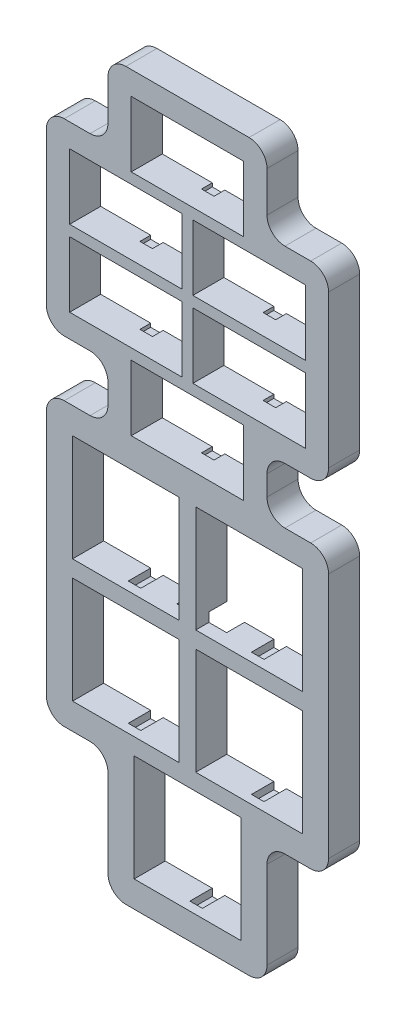
SolidWorks part; units mm, degrees
ref_plane "Front Plane" through (0, 0, 0) normal (0, 0, 1) x (1, 0, 0)
ref_plane "Top Plane" through (0, 0, 0) normal (0, 1, 0) x (1, 0, 0)
ref_plane "Right Plane" through (0, 0, 0) normal (1, 0, 0) x (0, 0, -1)
sketch "Sketch1" plane through (0, 0, 0) normal (0, 0, 1) x (1, 0, 0)
  line L0 (15.1765, -101.5047) -> (15.1765, -87.4077) construction
  line L1 (29.2735, -101.5047) -> (15.1765, -101.5047) construction
  line L2 (29.2735, -101.5047) -> (29.2735, -87.4077) construction
  line L3 (29.2735, -87.4077) -> (15.1765, -87.4077) construction
  line L4 (15.1765, -101.5047) -> (15.1765, -87.4077) construction
  line L5 (29.7815, -102.0127) -> (14.6685, -102.0127)
  line L6 (14.6685, -102.0127) -> (14.6685, -86.8997)
  line L7 (29.7815, -86.8997) -> (14.6685, -86.8997)
  line L8 (20.5423, -84.0423) -> (6.4453, -84.0423) construction
  line L9 (20.5423, -84.0423) -> (20.5423, -69.9453) construction
  line L10 (20.5423, -69.9453) -> (6.4453, -69.9453) construction
  line L11 (6.4453, -84.0423) -> (6.4453, -69.9453) construction
  line L12 (29.7815, -102.0127) -> (29.7815, -86.8997)
  line L13 (21.0503, -84.5503) -> (5.9373, -84.5503)
  line L14 (23.9078, -84.0422) -> (38.0048, -84.0422) construction
  line L15 (23.9078, -84.0422) -> (23.9078, -69.9452) construction
  line L16 (23.9078, -69.9452) -> (38.0048, -69.9452) construction
  line L17 (38.0048, -84.0422) -> (38.0048, -69.9452) construction
  line L18 (5.9373, -84.5503) -> (5.9373, -69.4373)
  line L19 (21.0503, -69.4373) -> (5.9373, -69.4373)
  line L20 (38.0048, -66.5797) -> (23.9078, -66.5797) construction
  line L21 (38.0048, -66.5797) -> (38.0048, -52.4827) construction
  line L22 (38.0048, -52.4827) -> (23.9078, -52.4827) construction
  line L23 (23.9078, -66.5797) -> (23.9078, -52.4827) construction
  line L24 (21.0503, -84.5503) -> (21.0503, -69.4373)
  line L25 (23.3998, -84.5502) -> (38.5128, -84.5502)
  line L26 (20.5423, -66.5798) -> (6.4453, -66.5797) construction
  line L27 (20.5423, -66.5798) -> (20.5423, -52.4827) construction
  line L28 (20.5423, -52.4827) -> (6.4453, -52.4828) construction
  line L29 (6.4453, -66.5797) -> (6.4453, -52.4828) construction
  line L30 (38.5128, -84.5502) -> (38.5128, -69.4372)
  line L31 (23.3998, -69.4372) -> (38.5128, -69.4372)
  line L32 (29.6863, -47.3075) -> (14.7638, -47.3075) construction
  line L33 (29.6863, -47.3075) -> (29.6863, -39.0525) construction
  line L34 (29.6863, -39.0525) -> (14.7638, -39.0525) construction
  line L35 (14.7638, -47.3075) -> (14.7638, -39.0525) construction
  line L36 (23.3998, -84.5502) -> (23.3998, -69.4372)
  line L37 (38.5128, -67.0877) -> (23.3998, -67.0877)
  line L38 (20.955, -36.5125) -> (6.0325, -36.5125) construction
  line L39 (20.955, -36.5125) -> (20.955, -28.2575) construction
  line L40 (20.955, -28.2575) -> (6.0325, -28.2575) construction
  line L41 (6.0325, -36.5125) -> (6.0325, -28.2575) construction
  line L42 (23.3998, -67.0877) -> (23.3998, -51.9747)
  line L43 (38.5128, -51.9747) -> (23.3998, -51.9747)
  line L44 (20.955, -25.7175) -> (6.0325, -25.7175) construction
  line L45 (20.955, -25.7175) -> (20.955, -17.4625) construction
  line L46 (20.955, -17.4625) -> (6.0325, -17.4625) construction
  line L47 (6.0325, -25.7175) -> (6.0325, -17.4625) construction
  line L48 (38.5128, -67.0877) -> (38.5128, -51.9747)
  line L49 (21.0503, -67.0877) -> (5.9373, -67.0877)
  line L50 (29.6863, -14.9225) -> (14.7638, -14.9225) construction
  line L51 (29.6863, -14.9225) -> (29.6863, -6.6675) construction
  line L52 (29.6863, -6.6675) -> (14.7638, -6.6675) construction
  line L53 (14.7638, -14.9225) -> (14.7638, -6.6675) construction
  line L54 (5.9373, -67.0877) -> (5.9373, -51.9747)
  line L55 (21.0503, -51.9747) -> (5.9373, -51.9747)
  line L56 (38.4175, -25.7175) -> (23.495, -25.7175) construction
  line L57 (38.4175, -25.7175) -> (38.4175, -17.4625) construction
  line L58 (38.4175, -17.4625) -> (23.495, -17.4625) construction
  line L59 (23.495, -25.7175) -> (23.495, -17.4625) construction
  line L60 (21.0503, -67.0877) -> (21.0503, -51.9747)
  line L61 (30.1943, -47.8155) -> (14.2558, -47.8155)
  line L62 (38.4175, -36.5125) -> (23.495, -36.5125) construction
  line L63 (38.4175, -36.5125) -> (38.4175, -28.2575) construction
  line L64 (38.4175, -28.2575) -> (23.495, -28.2575) construction
  line L65 (23.495, -36.5125) -> (23.495, -28.2575) construction
  line L66 (14.2558, -47.8155) -> (14.2558, -38.5445)
  line L67 (30.1943, -38.5445) -> (14.2558, -38.5445)
  line L68 (30.1943, -47.8155) -> (30.1943, -38.5445)
  line L69 (21.463, -37.0205) -> (5.5245, -37.0205)
  line L70 (5.5245, -37.0205) -> (5.5245, -27.7495)
  line L71 (21.463, -27.7495) -> (5.5245, -27.7495)
  line L72 (21.463, -37.0205) -> (21.463, -27.7495)
  line L73 (21.463, -26.2255) -> (5.5245, -26.2255)
  line L74 (5.5245, -26.2255) -> (5.5245, -16.9545)
  line L75 (21.463, -16.9545) -> (5.5245, -16.9545)
  line L76 (21.463, -26.2255) -> (21.463, -16.9545)
  line L77 (30.1943, -15.4305) -> (14.2558, -15.4305)
  line L78 (14.2558, -15.4305) -> (14.2558, -6.1595)
  line L79 (30.1943, -6.1595) -> (14.2558, -6.1595)
  line L80 (30.1943, -15.4305) -> (30.1943, -6.1595)
  line L81 (38.9255, -26.2255) -> (22.987, -26.2255)
  line L82 (22.987, -26.2255) -> (22.987, -16.9545)
  line L83 (38.9255, -16.9545) -> (22.987, -16.9545)
  line L84 (38.9255, -26.2255) -> (38.9255, -16.9545)
  line L85 (38.9255, -37.0205) -> (22.987, -37.0205)
  line L86 (22.987, -37.0205) -> (22.987, -27.7495)
  line L87 (38.9255, -27.7495) -> (22.987, -27.7495)
  line L88 (38.9255, -37.0205) -> (38.9255, -27.7495)
  line L97 (30.9563, -85.725) -> (39.6875, -85.725)
  line L98 (39.6875, -85.725) -> (39.6875, -50.8)
  line L99 (39.6875, -50.8) -> (4.7625, -50.8)
  line L100 (4.7625, -50.8) -> (4.7625, -85.725)
  line L101 (30.9563, -37.7825) -> (39.6875, -37.7825)
  line L102 (39.6875, -37.7825) -> (39.6875, -16.1925)
  line L103 (39.6875, -16.1925) -> (30.9563, -16.1925)
  line L104 (30.9563, -16.1925) -> (30.9563, -5.3975)
  line L105 (30.9563, -5.3975) -> (13.4938, -5.3975)
  line L106 (13.4938, -5.3975) -> (13.4938, -16.1925)
  line L107 (13.4938, -16.1925) -> (4.7625, -16.1925)
  line L108 (4.7625, -16.1925) -> (4.7625, -37.7825)
  line L109 (4.7625, -37.7825) -> (13.4938, -37.7825)
  line L110 (13.4938, -37.7825) -> (13.4938, -48.5775)
  line L111 (13.4938, -48.5775) -> (30.9563, -48.5775)
  line L112 (30.9563, -48.5775) -> (30.9563, -37.7825)
  line L113 (30.9563, -37.7825) -> (39.6875, -37.7825)
  line L114 (39.6875, -37.7825) -> (39.6875, -16.1925)
  line L115 (39.6875, -16.1925) -> (30.9563, -16.1925)
  line L116 (30.9563, -16.1925) -> (30.9563, -5.3975)
  line L117 (30.9563, -5.3975) -> (13.4938, -5.3975)
  line L118 (13.4938, -5.3975) -> (13.4938, -16.1925)
  line L119 (13.4938, -16.1925) -> (4.7625, -16.1925)
  line L120 (4.7625, -16.1925) -> (4.7625, -37.7825)
  line L121 (4.7625, -37.7825) -> (13.4938, -37.7825)
  line L122 (13.4938, -37.7825) -> (13.4938, -48.5775)
  line L124 (30.9563, -48.5775) -> (30.9563, -37.7825)
  line L125 (4.7625, -85.725) -> (13.4938, -85.725)
  line L126 (13.4938, -85.725) -> (13.4938, -103.1875)
  line L127 (13.4938, -103.1875) -> (30.9563, -103.1875)
  line L128 (30.9563, -103.1875) -> (30.9563, -85.725)
  line L129 (30.9563, -85.725) -> (39.6875, -85.725)
  line L130 (39.6875, -85.725) -> (39.6875, -50.8)
  line L131 (39.6875, -50.8) -> (30.9563, -50.8)
  line L132 (4.7625, -50.8) -> (4.7625, -85.725)
  line L133 (4.7625, -85.725) -> (13.4938, -85.725)
  line L134 (13.4938, -85.725) -> (13.4938, -103.1875)
  line L135 (13.4938, -103.1875) -> (30.9563, -103.1875)
  line L136 (30.9563, -103.1875) -> (30.9563, -85.725)
  line L2229 (13.4938, -50.8) -> (4.7625, -50.8)
  line L2231 (30.9563, -48.5775) -> (30.9563, -50.8)
  line L2233 (13.4938, -48.5775) -> (13.4938, -50.8)
  dimension "D1" = 0.508
  dimension "D2" = 0
  dimension "D3" = 0
extrude "Boss-Extrude1" add sketch "Sketch1" against normal up to surface (4.4025 mm away)
sketch "Sketch4" plane through (0, 0, -4.4025) normal (0, 0, -1) x (-1, 0, 0)
  line L40 (-30.9563, -37.7825) -> (-30.9563, -50.8)
  line L41 (-30.9563, -50.8) -> (-39.6875, -50.8)
  line L42 (-39.6875, -50.8) -> (-39.6875, -85.725)
  line L43 (-39.6875, -85.725) -> (-30.9563, -85.725)
  line L44 (-30.9563, -85.725) -> (-30.9563, -103.1875)
  line L45 (-30.9563, -103.1875) -> (-13.4938, -103.1875)
  line L46 (-13.4938, -103.1875) -> (-13.4938, -85.725)
  line L47 (-13.4938, -85.725) -> (-4.7625, -85.725)
  line L48 (-4.7625, -85.725) -> (-4.7625, -50.8)
  line L49 (-4.7625, -50.8) -> (-13.4938, -50.8)
  line L50 (-13.4938, -50.8) -> (-13.4938, -37.7825)
  line L51 (-13.4938, -37.7825) -> (-4.7625, -37.7825)
  line L52 (-4.7625, -37.7825) -> (-4.7625, -16.1925)
  line L53 (-4.7625, -16.1925) -> (-13.4938, -16.1925)
  line L54 (-13.4938, -16.1925) -> (-13.4938, -5.3975)
  line L55 (-13.4938, -5.3975) -> (-30.9563, -5.3975)
  line L56 (-30.9563, -5.3975) -> (-30.9563, -16.1925)
  line L57 (-30.9563, -16.1925) -> (-39.6875, -16.1925)
  line L58 (-39.6875, -16.1925) -> (-39.6875, -37.7825)
  line L59 (-39.6875, -37.7825) -> (-30.9563, -37.7825)
  line L60 (-30.9563, -37.7825) -> (-30.9563, -50.8)
  line L61 (-30.9563, -50.8) -> (-39.6875, -50.8)
  line L62 (-39.6875, -50.8) -> (-39.6875, -85.725)
  line L63 (-39.6875, -85.725) -> (-30.9563, -85.725)
  line L64 (-30.9563, -85.725) -> (-30.9563, -103.1875)
  line L65 (-30.9563, -103.1875) -> (-13.4938, -103.1875)
  line L66 (-13.4938, -103.1875) -> (-13.4938, -85.725)
  line L67 (-13.4938, -85.725) -> (-4.7625, -85.725)
  line L68 (-4.7625, -85.725) -> (-4.7625, -50.8)
  line L69 (-4.7625, -50.8) -> (-13.4938, -50.8)
  line L70 (-13.4938, -50.8) -> (-13.4938, -37.7825)
  line L71 (-13.4938, -37.7825) -> (-4.7625, -37.7825)
  line L72 (-4.7625, -37.7825) -> (-4.7625, -16.1925)
  line L73 (-4.7625, -16.1925) -> (-13.4938, -16.1925)
  line L74 (-13.4938, -16.1925) -> (-13.4938, -5.3975)
  line L75 (-13.4938, -5.3975) -> (-30.9563, -5.3975)
  line L76 (-30.9563, -5.3975) -> (-30.9563, -16.1925)
  line L77 (-30.9563, -16.1925) -> (-39.6875, -16.1925)
  line L78 (-39.6875, -16.1925) -> (-39.6875, -37.7825)
  line L79 (-39.6875, -37.7825) -> (-30.9563, -37.7825)
  dimension "D1" = 0
extrude "Extrude-Thin1" add sketch "Sketch4" against normal through all thin thin type one direction wall 2.54
fillet "Fillet1" radius 2.54 20 edges at (42.2275, -48.26, -2.2012) (2.2225, -13.6525, -2.2012) (10.9538, -2.8575, -2.2012) (33.4963, -2.8575, -2.2012) (42.2275, -13.6525, -2.2012) (42.2275, -40.3225, -2.2012) (2.2225, -40.3225, -2.2012) (2.2225, -48.26, -2.2012) (42.2275, -88.265, -2.2012) (33.4963, -105.7275, -2.2012) (10.9538, -105.7275, -2.2012) (2.2225, -88.265, -2.2012) (10.9538, -88.265, -2.2012) (33.4963, -88.265, -2.2012) (33.4963, -40.3225, -2.2012) (33.4963, -48.26, -2.2012) (10.9538, -48.26, -2.2012) (10.9538, -40.3225, -2.2012) (10.9538, -13.6525, -2.2012) (33.4963, -13.6525, -2.2012)
sketch "Sketch5" plane through (0, 0, -4.4025) normal (0, 0, -1) x (-1, 0, 0)
  line L0 (-14.2558, -6.1595) -> (-30.1943, -6.1595) construction
  line L1 (-26.5906, -6.1595) -> (-25.3206, -6.1595) construction
  line L2 (-26.5906, -6.1595) -> (-26.5906, -5.9065) construction
  line L3 (-26.5906, -5.9065) -> (-25.3206, -5.9065) construction
  line L4 (-25.3206, -6.1595) -> (-25.3206, -5.9065) construction
  line L5 (-19.1294, -6.1595) -> (-17.8594, -6.1595) construction
  line L6 (-19.1294, -6.1595) -> (-19.1294, -5.9065) construction
  line L7 (-19.1294, -5.9065) -> (-17.8594, -5.9065) construction
  line L8 (-17.8594, -6.1595) -> (-17.8594, -5.9065) construction
  line L9 (-21.59, -15.6835) -> (-21.59, -15.4305) construction
  line L10 (-22.86, -15.6835) -> (-21.59, -15.6835) construction
  line L11 (-22.86, -15.6835) -> (-22.86, -15.4305) construction
  line L12 (-22.86, -15.4305) -> (-21.59, -15.4305) construction
  line L13 (-35.3219, -16.7015) -> (-34.0519, -16.7015) construction
  line L14 (-27.8606, -16.7015) -> (-26.5906, -16.7015) construction
  line L15 (-30.3213, -26.4785) -> (-30.3213, -26.2255) construction
  line L16 (-31.5913, -26.4785) -> (-30.3213, -26.4785) construction
  line L17 (-35.3219, -16.9545) -> (-34.0519, -16.9545) construction
  line L18 (-34.0519, -16.9545) -> (-34.0519, -16.7015) construction
  line L19 (-27.8606, -16.9545) -> (-26.5906, -16.9545) construction
  line L20 (-26.5906, -16.9545) -> (-26.5906, -16.7015) construction
  line L21 (-31.5913, -26.2255) -> (-30.3213, -26.2255) construction
  line L22 (-27.8606, -16.9545) -> (-27.8606, -16.7015) construction
  line L23 (-31.5913, -26.4785) -> (-31.5913, -26.2255) construction
  line L24 (-35.3219, -16.9545) -> (-35.3219, -16.7015) construction
  line L25 (-12.8588, -26.4785) -> (-12.8588, -26.2255) construction
  line L26 (-16.5894, -16.9545) -> (-16.5894, -16.7015) construction
  line L27 (-10.3981, -16.9545) -> (-10.3981, -16.7015) construction
  line L28 (-14.1288, -26.4785) -> (-12.8588, -26.4785) construction
  line L29 (-14.1288, -26.4785) -> (-14.1288, -26.2255) construction
  line L30 (-17.8594, -16.7015) -> (-16.5894, -16.7015) construction
  line L31 (-9.1281, -16.9545) -> (-9.1281, -16.7015) construction
  line L32 (-14.1288, -26.2255) -> (-12.8588, -26.2255) construction
  line L33 (-17.8594, -16.9545) -> (-16.5894, -16.9545) construction
  line L34 (-10.3981, -16.9545) -> (-9.1281, -16.9545) construction
  line L35 (-17.8594, -16.9545) -> (-17.8594, -16.7015) construction
  line L36 (-10.3981, -16.7015) -> (-9.1281, -16.7015) construction
  line L37 (-30.3213, -37.2735) -> (-30.3213, -37.0205) construction
  line L38 (-31.5913, -37.2735) -> (-31.5913, -37.0205) construction
  line L39 (-27.8606, -27.7495) -> (-26.5906, -27.7495) construction
  line L40 (-10.3981, -27.7495) -> (-10.3981, -27.4965) construction
  line L41 (-17.8594, -27.4965) -> (-16.5894, -27.4965) construction
  line L42 (-31.5913, -37.0205) -> (-30.3213, -37.0205) construction
  line L43 (-14.1287, -37.2735) -> (-12.8587, -37.2735) construction
  line L44 (-35.3219, -27.4965) -> (-34.0519, -27.4965) construction
  line L45 (-31.5913, -37.2735) -> (-30.3213, -37.2735) construction
  line L46 (-12.8587, -37.2735) -> (-12.8587, -37.0205) construction
  line L47 (-26.5906, -27.7495) -> (-26.5906, -27.4965) construction
  line L48 (-9.1281, -27.7495) -> (-9.1281, -27.4965) construction
  line L49 (-16.5894, -27.7495) -> (-16.5894, -27.4965) construction
  line L50 (-17.8594, -27.7495) -> (-16.5894, -27.7495) construction
  line L51 (-27.8606, -27.7495) -> (-27.8606, -27.4965) construction
  line L52 (-10.3981, -27.7495) -> (-9.1281, -27.7495) construction
  line L53 (-34.0519, -27.7495) -> (-34.0519, -27.4965) construction
  line L54 (-35.3219, -27.7495) -> (-35.3219, -27.4965) construction
  line L55 (-17.8594, -27.7495) -> (-17.8594, -27.4965) construction
  line L56 (-35.3219, -27.7495) -> (-34.0519, -27.7495) construction
  line L57 (-14.1287, -37.2735) -> (-14.1287, -37.0205) construction
  line L58 (-14.1287, -37.0205) -> (-12.8587, -37.0205) construction
  line L59 (-27.8606, -27.4965) -> (-26.5906, -27.4965) construction
  line L60 (-10.3981, -27.4965) -> (-9.1281, -27.4965) construction
  line L61 (-22.86, -47.8155) -> (-21.59, -47.8155) construction
  line L62 (-26.5906, -38.5445) -> (-26.5906, -38.2915) construction
  line L63 (-21.59, -48.0685) -> (-21.59, -47.8155) construction
  line L64 (-25.3206, -38.5445) -> (-25.3206, -38.2915) construction
  line L65 (-22.86, -48.0685) -> (-21.59, -48.0685) construction
  line L66 (-19.1294, -38.5445) -> (-17.8594, -38.5445) construction
  line L67 (-19.1294, -38.2915) -> (-17.8594, -38.2915) construction
  line L68 (-26.5906, -38.5445) -> (-25.3206, -38.5445) construction
  line L69 (-22.86, -48.0685) -> (-22.86, -47.8155) construction
  line L70 (-19.1294, -38.5445) -> (-19.1294, -38.2915) construction
  line L71 (-17.8594, -38.5445) -> (-17.8594, -38.2915) construction
  line L72 (-26.5906, -38.2915) -> (-25.3206, -38.2915) construction
  line L73 (-26.8446, -6.4135) -> (-25.0666, -6.4135)
  line L74 (-25.0666, -6.4135) -> (-25.0666, -5.6525)
  line L75 (-26.8446, -5.6525) -> (-25.0666, -5.6525)
  line L76 (-26.8446, -6.4135) -> (-26.8446, -5.6525)
  line L77 (-19.3834, -6.4135) -> (-17.6054, -6.4135)
  line L78 (-17.6054, -6.4135) -> (-17.6054, -5.6525)
  line L79 (-19.3834, -5.6525) -> (-17.6054, -5.6525)
  line L80 (-19.3834, -6.4135) -> (-19.3834, -5.6525)
  line L81 (-21.336, -15.9375) -> (-21.336, -15.1765)
  line L82 (-23.114, -15.1765) -> (-21.336, -15.1765)
  line L83 (-23.114, -15.9375) -> (-23.114, -15.1765)
  line L84 (-23.114, -15.9375) -> (-21.336, -15.9375)
  line L85 (-35.5759, -16.4475) -> (-33.7979, -16.4475)
  line L86 (-33.7979, -17.2085) -> (-33.7979, -16.4475)
  line L87 (-35.5759, -17.2085) -> (-33.7979, -17.2085)
  line L88 (-35.5759, -17.2085) -> (-35.5759, -16.4475)
  line L89 (-28.1146, -16.4475) -> (-26.3366, -16.4475)
  line L90 (-26.3366, -17.2085) -> (-26.3366, -16.4475)
  line L91 (-28.1146, -17.2085) -> (-26.3366, -17.2085)
  line L92 (-28.1146, -17.2085) -> (-28.1146, -16.4475)
  line L93 (-30.0673, -26.7325) -> (-30.0673, -25.9715)
  line L94 (-31.8453, -25.9715) -> (-30.0673, -25.9715)
  line L95 (-31.8453, -26.7325) -> (-31.8453, -25.9715)
  line L96 (-31.8453, -26.7325) -> (-30.0673, -26.7325)
  line L97 (-12.6048, -26.7325) -> (-12.6048, -25.9715)
  line L98 (-14.3828, -25.9715) -> (-12.6048, -25.9715)
  line L99 (-14.3828, -26.7325) -> (-14.3828, -25.9715)
  line L100 (-14.3828, -26.7325) -> (-12.6048, -26.7325)
  line L101 (-16.3354, -17.2085) -> (-16.3354, -16.4475)
  line L102 (-18.1134, -16.4475) -> (-16.3354, -16.4475)
  line L103 (-18.1134, -17.2085) -> (-18.1134, -16.4475)
  line L104 (-18.1134, -17.2085) -> (-16.3354, -17.2085)
  line L105 (-10.6521, -17.2085) -> (-10.6521, -16.4475)
  line L106 (-10.6521, -16.4475) -> (-8.8741, -16.4475)
  line L107 (-8.8741, -17.2085) -> (-8.8741, -16.4475)
  line L108 (-10.6521, -17.2085) -> (-8.8741, -17.2085)
  line L109 (-30.0673, -37.5275) -> (-30.0673, -36.7665)
  line L110 (-31.8453, -36.7665) -> (-30.0673, -36.7665)
  line L111 (-31.8453, -37.5275) -> (-31.8453, -36.7665)
  line L112 (-31.8453, -37.5275) -> (-30.0673, -37.5275)
  line L113 (-28.1146, -28.0035) -> (-26.3366, -28.0035)
  line L114 (-26.3366, -28.0035) -> (-26.3366, -27.2425)
  line L115 (-28.1146, -27.2425) -> (-26.3366, -27.2425)
  line L116 (-28.1146, -28.0035) -> (-28.1146, -27.2425)
  line L117 (-10.6521, -28.0035) -> (-10.6521, -27.2425)
  line L118 (-10.6521, -27.2425) -> (-8.8741, -27.2425)
  line L119 (-8.8741, -28.0035) -> (-8.8741, -27.2425)
  line L120 (-10.6521, -28.0035) -> (-8.8741, -28.0035)
  line L121 (-18.1134, -27.2425) -> (-16.3354, -27.2425)
  line L122 (-16.3354, -28.0035) -> (-16.3354, -27.2425)
  line L123 (-18.1134, -28.0035) -> (-16.3354, -28.0035)
  line L124 (-18.1134, -28.0035) -> (-18.1134, -27.2425)
  line L125 (-14.3827, -37.5275) -> (-12.6047, -37.5275)
  line L126 (-12.6047, -37.5275) -> (-12.6047, -36.7665)
  line L127 (-14.3827, -36.7665) -> (-12.6047, -36.7665)
  line L128 (-14.3827, -37.5275) -> (-14.3827, -36.7665)
  line L129 (-35.5759, -27.2425) -> (-33.7979, -27.2425)
  line L130 (-33.7979, -28.0035) -> (-33.7979, -27.2425)
  line L131 (-35.5759, -28.0035) -> (-33.7979, -28.0035)
  line L132 (-35.5759, -28.0035) -> (-35.5759, -27.2425)
  line L133 (-23.114, -47.5615) -> (-21.336, -47.5615)
  line L134 (-21.336, -48.3225) -> (-21.336, -47.5615)
  line L135 (-23.114, -48.3225) -> (-21.336, -48.3225)
  line L136 (-23.114, -48.3225) -> (-23.114, -47.5615)
  line L137 (-26.8446, -38.7985) -> (-26.8446, -38.0375)
  line L138 (-26.8446, -38.0375) -> (-25.0666, -38.0375)
  line L139 (-25.0666, -38.7985) -> (-25.0666, -38.0375)
  line L140 (-26.8446, -38.7985) -> (-25.0666, -38.7985)
  line L141 (-19.3834, -38.7985) -> (-17.6054, -38.7985)
  line L142 (-17.6054, -38.7985) -> (-17.6054, -38.0375)
  line L143 (-19.3834, -38.0375) -> (-17.6054, -38.0375)
  line L144 (-19.3834, -38.7985) -> (-19.3834, -38.0375)
  dimension "D1" = 0.254
extrude "Cut-Extrude1" cut sketch "Sketch5" against normal blind 1.524
sketch "Sketch6" plane through (0, 0, -4.4025) normal (0, 0, -1) x (-1, 0, 0)
  line L0 (-23.3998, -51.9747) -> (-38.5128, -51.9747) construction
  line L1 (-35.1155, -51.9747) -> (-33.8455, -51.9747) construction
  line L2 (-35.1155, -51.9747) -> (-35.1155, -51.2127) construction
  line L3 (-35.1155, -51.2127) -> (-33.8455, -51.2127) construction
  line L4 (-33.8455, -51.9747) -> (-33.8455, -51.2127) construction
  line L5 (-28.067, -51.9747) -> (-28.067, -51.2127) construction
  line L6 (-28.067, -51.2127) -> (-26.797, -51.2127) construction
  line L7 (-28.067, -51.9747) -> (-26.797, -51.9747) construction
  line L8 (-26.797, -51.9747) -> (-26.797, -51.2127) construction
  line L9 (-30.3213, -67.8497) -> (-30.3213, -67.0877) construction
  line L10 (-31.5913, -67.8497) -> (-31.5913, -67.0877) construction
  line L11 (-31.5913, -67.0877) -> (-30.3213, -67.0877) construction
  line L12 (-31.5913, -67.8497) -> (-30.3213, -67.8497) construction
  line L13 (-10.6045, -51.9748) -> (-10.6045, -51.2128) construction
  line L14 (-12.8588, -67.8498) -> (-12.8588, -67.0878) construction
  line L15 (-17.653, -51.9748) -> (-17.653, -51.2128) construction
  line L16 (-16.383, -51.9748) -> (-16.383, -51.2128) construction
  line L17 (-10.6045, -51.9748) -> (-9.3345, -51.9748) construction
  line L18 (-9.3345, -51.9748) -> (-9.3345, -51.2128) construction
  line L19 (-10.6045, -51.2128) -> (-9.3345, -51.2128) construction
  line L20 (-14.1288, -67.8498) -> (-12.8588, -67.8498) construction
  line L21 (-17.653, -51.9748) -> (-16.383, -51.9748) construction
  line L22 (-14.1288, -67.8498) -> (-14.1288, -67.0878) construction
  line L23 (-17.653, -51.2128) -> (-16.383, -51.2128) construction
  line L24 (-14.1288, -67.0878) -> (-12.8588, -67.0878) construction
  line L25 (-30.3213, -85.3122) -> (-30.3213, -84.5502) construction
  line L26 (-31.5913, -85.3122) -> (-30.3213, -85.3122) construction
  line L27 (-14.1288, -84.5503) -> (-12.8588, -84.5503) construction
  line L28 (-35.1155, -69.4372) -> (-33.8455, -69.4372) construction
  line L29 (-9.3345, -69.4373) -> (-9.3345, -68.6753) construction
  line L30 (-35.1155, -68.6752) -> (-33.8455, -68.6752) construction
  line L31 (-17.653, -69.4373) -> (-16.383, -69.4373) construction
  line L32 (-17.653, -68.6753) -> (-16.383, -68.6753) construction
  line L33 (-28.067, -68.6752) -> (-26.797, -68.6752) construction
  line L34 (-17.653, -69.4373) -> (-17.653, -68.6753) construction
  line L35 (-35.1155, -69.4372) -> (-35.1155, -68.6752) construction
  line L36 (-31.5913, -85.3122) -> (-31.5913, -84.5502) construction
  line L37 (-12.8588, -85.3123) -> (-12.8588, -84.5503) construction
  line L38 (-28.067, -69.4372) -> (-26.797, -69.4372) construction
  line L39 (-14.1288, -85.3123) -> (-12.8588, -85.3123) construction
  line L40 (-16.383, -69.4373) -> (-16.383, -68.6753) construction
  line L41 (-31.5913, -84.5502) -> (-30.3213, -84.5502) construction
  line L42 (-33.8455, -69.4372) -> (-33.8455, -68.6752) construction
  line L43 (-28.067, -69.4372) -> (-28.067, -68.6752) construction
  line L44 (-26.797, -69.4372) -> (-26.797, -68.6752) construction
  line L45 (-10.6045, -69.4373) -> (-9.3345, -69.4373) construction
  line L46 (-14.1288, -85.3123) -> (-14.1288, -84.5503) construction
  line L47 (-10.6045, -68.6753) -> (-9.3345, -68.6753) construction
  line L48 (-10.6045, -69.4373) -> (-10.6045, -68.6753) construction
  line L49 (-26.3843, -86.8997) -> (-25.1143, -86.8997) construction
  line L50 (-21.59, -102.7747) -> (-21.59, -102.0127) construction
  line L51 (-22.86, -102.7747) -> (-22.86, -102.0127) construction
  line L52 (-26.3843, -86.1377) -> (-25.1143, -86.1377) construction
  line L53 (-22.86, -102.7747) -> (-21.59, -102.7747) construction
  line L54 (-22.86, -102.0127) -> (-21.59, -102.0127) construction
  line L55 (-19.3358, -86.1377) -> (-18.0658, -86.1377) construction
  line L56 (-26.3843, -86.8997) -> (-26.3843, -86.1377) construction
  line L57 (-25.1143, -86.8997) -> (-25.1143, -86.1377) construction
  line L58 (-18.0658, -86.8997) -> (-18.0658, -86.1377) construction
  line L59 (-19.3358, -86.8997) -> (-19.3358, -86.1377) construction
  line L60 (-19.3358, -86.8997) -> (-18.0658, -86.8997) construction
  line L61 (-35.3695, -52.2287) -> (-33.5915, -52.2287)
  line L62 (-33.5915, -52.2287) -> (-33.5915, -50.9587)
  line L63 (-35.3695, -50.9587) -> (-33.5915, -50.9587)
  line L64 (-35.3695, -52.2287) -> (-35.3695, -50.9587)
  line L65 (-28.321, -52.2287) -> (-28.321, -50.9587)
  line L66 (-28.321, -50.9587) -> (-26.543, -50.9587)
  line L67 (-26.543, -52.2287) -> (-26.543, -50.9587)
  line L68 (-28.321, -52.2287) -> (-26.543, -52.2287)
  line L69 (-30.0673, -68.1037) -> (-30.0673, -66.8337)
  line L70 (-31.8453, -66.8337) -> (-30.0673, -66.8337)
  line L71 (-31.8453, -68.1037) -> (-31.8453, -66.8337)
  line L72 (-31.8453, -68.1037) -> (-30.0673, -68.1037)
  line L73 (-10.8585, -52.2288) -> (-10.8585, -50.9588)
  line L74 (-10.8585, -50.9588) -> (-9.0805, -50.9588)
  line L75 (-9.0805, -52.2288) -> (-9.0805, -50.9588)
  line L76 (-10.8585, -52.2288) -> (-9.0805, -52.2288)
  line L77 (-12.6048, -68.1038) -> (-12.6048, -66.8338)
  line L78 (-14.3828, -66.8338) -> (-12.6048, -66.8338)
  line L79 (-14.3828, -68.1038) -> (-14.3828, -66.8338)
  line L80 (-14.3828, -68.1038) -> (-12.6048, -68.1038)
  line L81 (-17.907, -52.2288) -> (-17.907, -50.9588)
  line L82 (-17.907, -50.9588) -> (-16.129, -50.9588)
  line L83 (-16.129, -52.2288) -> (-16.129, -50.9588)
  line L84 (-17.907, -52.2288) -> (-16.129, -52.2288)
  line L85 (-30.0673, -85.5662) -> (-30.0673, -84.2962)
  line L86 (-31.8453, -84.2962) -> (-30.0673, -84.2962)
  line L87 (-31.8453, -85.5662) -> (-31.8453, -84.2962)
  line L88 (-31.8453, -85.5662) -> (-30.0673, -85.5662)
  line L89 (-14.3828, -84.2963) -> (-12.6048, -84.2963)
  line L90 (-12.6048, -85.5663) -> (-12.6048, -84.2963)
  line L91 (-14.3828, -85.5663) -> (-12.6048, -85.5663)
  line L92 (-14.3828, -85.5663) -> (-14.3828, -84.2963)
  line L93 (-35.3695, -69.6912) -> (-33.5915, -69.6912)
  line L94 (-33.5915, -69.6912) -> (-33.5915, -68.4212)
  line L95 (-35.3695, -68.4212) -> (-33.5915, -68.4212)
  line L96 (-35.3695, -69.6912) -> (-35.3695, -68.4212)
  line L97 (-9.0805, -69.6913) -> (-9.0805, -68.4213)
  line L98 (-10.8585, -68.4213) -> (-9.0805, -68.4213)
  line L99 (-10.8585, -69.6913) -> (-10.8585, -68.4213)
  line L100 (-10.8585, -69.6913) -> (-9.0805, -69.6913)
  line L101 (-17.907, -69.6913) -> (-16.129, -69.6913)
  line L102 (-16.129, -69.6913) -> (-16.129, -68.4213)
  line L103 (-17.907, -68.4213) -> (-16.129, -68.4213)
  line L104 (-17.907, -69.6913) -> (-17.907, -68.4213)
  line L105 (-28.321, -68.4212) -> (-26.543, -68.4212)
  line L106 (-26.543, -69.6912) -> (-26.543, -68.4212)
  line L107 (-28.321, -69.6912) -> (-26.543, -69.6912)
  line L108 (-28.321, -69.6912) -> (-28.321, -68.4212)
  line L109 (-26.6383, -87.1537) -> (-24.8603, -87.1537)
  line L110 (-24.8603, -87.1537) -> (-24.8603, -85.8837)
  line L111 (-26.6383, -85.8837) -> (-24.8603, -85.8837)
  line L112 (-26.6383, -87.1537) -> (-26.6383, -85.8837)
  line L113 (-21.336, -103.0287) -> (-21.336, -101.7587)
  line L114 (-23.114, -101.7587) -> (-21.336, -101.7587)
  line L115 (-23.114, -103.0287) -> (-23.114, -101.7587)
  line L116 (-23.114, -103.0287) -> (-21.336, -103.0287)
  line L117 (-19.5898, -85.8837) -> (-17.8118, -85.8837)
  line L118 (-17.8118, -87.1537) -> (-17.8118, -85.8837)
  line L119 (-19.5898, -87.1537) -> (-17.8118, -87.1537)
  line L120 (-19.5898, -87.1537) -> (-19.5898, -85.8837)
  point P7 (-34.0995, -51.2127)
  point P11 (-27.051, -51.2127)
  point P16 (-30.5753, -67.0877)
  point P22 (-16.637, -51.2128)
  point P26 (-9.5885, -51.2128)
  point P31 (-13.1128, -67.0878)
  point P37 (-34.0995, -68.6752)
  point P41 (-27.051, -68.6752)
  point P46 (-30.5753, -84.5502)
  point P52 (-16.637, -68.6753)
  point P56 (-9.5885, -68.6753)
  point P61 (-13.1128, -84.5503)
  point P67 (-25.3683, -86.1377)
  point P71 (-18.3198, -86.1377)
  point P76 (-21.844, -102.0127)
  dimension "D1" = 0.254
extrude "Cut-Extrude2" cut sketch "Sketch6" against normal blind 3.175
sketch "Sketch7" plane through (0, 0, -4.4025) normal (0, 0, 1) x (1, 0, 0)
  line L0 (38.5128, -51.9747) -> (23.3998, -51.9747) construction
  line L1 (35.7688, -49.6391) -> (40.3733, -49.6391)
  line L2 (35.7688, -49.6391) -> (35.7688, -56.0314)
  line L3 (35.7688, -56.0314) -> (40.3733, -56.0314)
  line L4 (40.3733, -49.6391) -> (40.3733, -56.0314)
  line L11 (21.0503, -51.9747) -> (23.3997, -51.9747) construction
  line L16 (21.0503, -67.0877) -> (21.0503, -51.9747) construction
  line L17 (23.3998, -51.9747) -> (23.3998, -67.0877) construction
  line L18 (22.225, -51.9747) -> (22.225, -47.8155) construction
  line L19 (14.2558, -47.8155) -> (30.1943, -47.8155) construction
  line L28 (31.7431, -50.6413) -> (31.7431, -51.9747) construction
  line L29 (32.7431, -50.6413) -> (32.7431, -51.9747)
  line L30 (30.7431, -50.6413) -> (30.7431, -51.9747)
  line L31 (27.5431, -50.6413) -> (27.5431, -51.9747) construction
  line L32 (28.5431, -50.6413) -> (28.5431, -51.9747)
  line L33 (26.5431, -50.6413) -> (26.5431, -51.9747)
  line L34 (16.5031, -50.6413) -> (16.5031, -51.9747) construction
  line L35 (21.0503, -51.9747) -> (5.9373, -51.9747) construction
  line L36 (17.5031, -50.6413) -> (17.5031, -51.9747)
  line L37 (15.5031, -50.6413) -> (15.5031, -51.9747)
  line L38 (12.3031, -50.6413) -> (12.3031, -51.9747) construction
  line L39 (13.3031, -50.6413) -> (13.3031, -51.9747)
  line L40 (11.3031, -50.6413) -> (11.3031, -51.9747)
  line L42 (18.8416, -65.7965) -> (25.9134, -65.7965)
  line L43 (18.8416, -65.7965) -> (18.8416, -70.9328)
  line L44 (18.8416, -70.9328) -> (25.9134, -70.9328)
  line L45 (25.9134, -65.7965) -> (25.9134, -70.9328)
  circle A0 centre (31.7431, -45.1413) radius 1
  arc A1 (32.7431, -50.6413) -> (30.7431, -50.6413) centre (31.7431, -50.6413) ccw
  arc A2 (30.7431, -51.9747) -> (32.7431, -51.9747) centre (31.7431, -51.9747) ccw
  arc A3 (28.5431, -50.6413) -> (26.5431, -50.6413) centre (27.5431, -50.6413) ccw
  arc A4 (26.5431, -51.9747) -> (28.5431, -51.9747) centre (27.5431, -51.9747) ccw
  arc A5 (17.5031, -50.6413) -> (15.5031, -50.6413) centre (16.5031, -50.6413) ccw
  arc A6 (15.5031, -51.9747) -> (17.5031, -51.9747) centre (16.5031, -51.9747) ccw
  arc A7 (13.3031, -50.6413) -> (11.3031, -50.6413) centre (12.3031, -50.6413) ccw
  arc A8 (11.3031, -51.9747) -> (13.3031, -51.9747) centre (12.3031, -51.9747) ccw
  circle A9 centre (12.3031, -45.1413) radius 1
  point P10 (31.7431, -51.308)
  point P15 (27.5431, -51.308)
  point P36 (16.5031, -51.308)
  point P41 (12.3031, -51.308)
  dimension "D1" = 2
extrude "Cut-Extrude3" cut sketch "Sketch7" along normal blind 2.54
